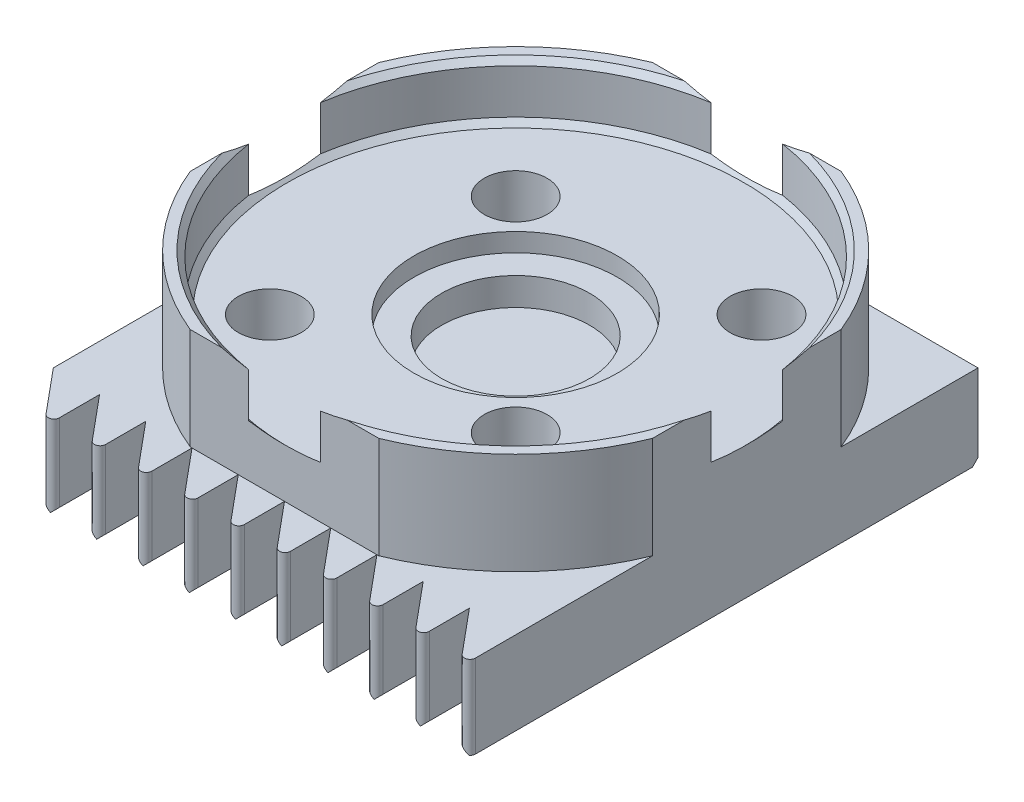
SolidWorks part; units mm, degrees
ref_plane "Front Plane" through (0, 0, 0) normal (0, 0, 1) x (1, 0, 0)
ref_plane "Top Plane" through (0, 0, 0) normal (0, 1, 0) x (1, 0, 0)
ref_plane "Right Plane" through (0, 0, 0) normal (1, 0, 0) x (0, 0, -1)
sketch "Sketch1" plane through (0, 0, 0) normal (0, 1, 0) x (1, 0, 0)
  line L0 (-6.6468, -6.6468) -> (6.6468, 6.6468) construction
  line L1 (-5.5331, 5.5331) -> (5.5331, -5.5331) construction
  line L2 (0, 0) -> (0, 3.1277) construction
  circle A0 centre (0, 0) radius 13.5
  circle A1 centre (0, 0) radius 5.5
  circle A2 centre (0, 0) radius 7.825 construction
  circle A3 centre (-5.5331, 5.5331) radius 1.7
  circle A4 centre (5.5331, -5.5331) radius 1.7
  circle A5 centre (0, 0) radius 9.4 construction
  circle A6 centre (-6.6468, -6.6468) radius 1.7
  circle A7 centre (6.6468, 6.6468) radius 1.7
  dimension "D1" = 27
  dimension "D2" = 11
  dimension "D3" = 15.65
  dimension "D4" = 18.8
  dimension "D5" = 3.4
  dimension "D6" = 45
extrude "Boss-Extrude1" add sketch "Sketch1" along normal blind 2.5 contours A0 A7 A6 A4 A3 A1 region at (-13.1182, 0, 0)
sketch "Sketch2" plane through (0, 2.5, 0) normal (0, 1, 0) x (1, 0, 0)
  circle A0 centre (0, 0) radius 12.65
  circle M6 centre (0, 0) radius 13.5
extrude "Boss-Extrude2" add sketch "Sketch2" along normal blind 3 contours A0 M6 region at (-13.1182, 2.5, 0)
sketch "Sketch3" plane through (0, 0, 0) normal (0, -1, 0) x (1, 0, 0)
  line L1 (12.5, -12.5) -> (-12.5, -12.5)
  line L2 (12.5, -12.5) -> (12.5, 12.5)
  line L3 (12.5, 12.5) -> (-12.5, 12.5)
  line L4 (-12.5, -12.5) -> (-12.5, 12.5)
  line L5 (12.5, -12.5) -> (-12.5, 12.5) construction
  line L6 (12.5, 12.5) -> (-12.5, -12.5) construction
  circle A0 centre (-5.5331, -5.5331) radius 1.7 construction
  circle A1 centre (6.6468, -6.6468) radius 1.7 construction
  circle A2 centre (5.5331, 5.5331) radius 1.7 construction
  circle A3 centre (-6.6468, 6.6468) radius 1.7 construction
  circle A4 centre (-5.5331, -5.5331) radius 1.7 construction
  circle A5 centre (6.6468, -6.6468) radius 1.7 construction
  circle A6 centre (5.5331, 5.5331) radius 1.7 construction
  circle A7 centre (-6.6468, 6.6468) radius 1.7 construction
  circle A8 centre (-6.6468, 6.6468) radius 3
  circle A9 centre (5.5331, 5.5331) radius 3
  circle A10 centre (6.6468, -6.6468) radius 3
  circle A11 centre (-5.5331, -5.5331) radius 3
  point P0 (0, 0)
  circle M5 centre (0, 0) radius 5.5
  circle M6 centre (0, 0) radius 13.5
  dimension "D1" = 6
  dimension "D2" = 25
extrude "Boss-Extrude3" add sketch "Sketch3" along normal blind 4.5 contours L4 L1 L2 L3 A11 A9 A10 A8 M6 M5 | L4 L3 M6 | L4 L1 M6 | L1 L2 M6 | L2 L3 M6 | A11 A9 M5 region at (10.3804, 0, -10.3804) region at (0, 0, -12.1464) region at (-10.3804, 0, -10.3804) region at (10.3804, 0, 10.3804) region at (-10.3804, 0, 10.3804) region at (0, 0, 0)
chamfer "Chamfer2" distance 0.3 angle 45 1 edges at (0, 2.5, 12.65)
sketch "Sketch4" plane through (0, 0, 0) normal (0, 1, 0) x (1, 0, 0)
  circle A0 centre (0, 0) radius 5.5 construction
  circle A1 centre (0, 0) radius 5.5
  circle A2 centre (0, 0) radius 4
  arc M1 (2.6146, -4.8388) -> (4.8388, -2.6146) centre (5.5331, -5.5331) cw
  arc M2 (4.8388, -2.6146) -> (-2.6146, 4.8388) centre (0, 0) ccw
  arc M3 (-2.6146, 4.8388) -> (-4.8388, 2.6146) centre (-5.5331, 5.5331) cw
  arc M4 (-4.8388, 2.6146) -> (2.6146, -4.8388) centre (0, 0) ccw
  dimension "D1" = 8
extrude "Boss-Extrude4" add sketch "Sketch4" along normal blind 1.5 contours A2 M4 M1 M2 M3 | A1 M3 | A1 M1 region at (5.1813, 0, 1.3103) region at (-3.6647, 0, -3.6647) region at (3.6647, 0, 3.6647)
sketch "Sketch6" plane through (0, 0, 0) normal (0, -1, 0) x (1, 0, 0)
  line L0 (5.099, -12.5) -> (-5.099, -12.5) construction
  line L1 (12.5, 5.099) -> (12.5, -5.099) construction
  line L2 (-5.099, 12.5) -> (5.099, 12.5) construction
  line L3 (-12.5, -5.099) -> (-12.5, 5.099) construction
  line L4 (5.099, -12.5) -> (-5.099, -12.5)
  line L5 (12.5, 5.099) -> (12.5, -5.099)
  line L6 (-5.099, 12.5) -> (5.099, 12.5)
  line L7 (-12.5, -5.099) -> (-12.5, 5.099)
  arc A0 (-5.099, -12.5) -> (5.099, -12.5) centre (0, 0) ccw construction
  arc A1 (12.5, -5.099) -> (12.5, 5.099) centre (0, 0) ccw construction
  arc A2 (5.099, 12.5) -> (-5.099, 12.5) centre (0, 0) ccw construction
  arc A3 (-12.5, 5.099) -> (-12.5, -5.099) centre (0, 0) ccw construction
  arc A4 (-5.099, -12.5) -> (5.099, -12.5) centre (0, 0) ccw
  arc A5 (12.5, -5.099) -> (12.5, 5.099) centre (0, 0) ccw
  arc A6 (5.099, 12.5) -> (-5.099, 12.5) centre (0, 0) ccw
  arc A7 (-12.5, 5.099) -> (-12.5, -5.099) centre (0, 0) ccw
extrude "Cut-Extrude1" cut sketch "Sketch6" against normal through all
chamfer "Chamfer3" distance 0.3 angle 45 4 edges at (8.9449, 5.5, -8.9449) (-8.9449, 5.5, -8.9449) (-8.9449, 5.5, 8.9449) (8.9449, 5.5, 8.9449)
sketch "Sketch7" plane through (0, -4.5, 0) normal (0, -1, 0) x (1, 0, 0)
  line L0 (12.5, 12.5) -> (-12.5, 12.5) construction
  line L1 (12.5, 12.5) -> (-12.5, 12.5)
  line L2 (-12.5, 12.5) -> (-10, 15.5)
  line L3 (-10, 15.5) -> (-10, 12.5)
  line L4 (-7.5, 15.5) -> (-7.5, 12.5)
  line L5 (-10, 12.5) -> (-7.5, 15.5)
  line L6 (-5, 15.5) -> (-5, 12.5)
  line L7 (-7.5, 12.5) -> (-5, 15.5)
  line L8 (-2.5, 15.5) -> (-2.5, 12.5)
  line L9 (-5, 12.5) -> (-2.5, 15.5)
  line L10 (0, 15.5) -> (0, 12.5)
  line L11 (-2.5, 12.5) -> (0, 15.5)
  line L12 (2.5, 15.5) -> (2.5, 12.5)
  line L13 (0, 12.5) -> (2.5, 15.5)
  line L14 (5, 15.5) -> (5, 12.5)
  line L15 (2.5, 12.5) -> (5, 15.5)
  line L16 (7.5, 15.5) -> (7.5, 12.5)
  line L17 (5, 12.5) -> (7.5, 15.5)
  line L18 (10, 15.5) -> (10, 12.5)
  line L19 (7.5, 12.5) -> (10, 15.5)
  line L20 (12.5, 15.5) -> (12.5, 12.5)
  line L21 (10, 12.5) -> (12.5, 15.5)
  line M9 (12.5, 12.5) -> (-12.5, 12.5)
  dimension "D1" = 3
  dimension "D2" = 2.5
  dimension "D3" = 10
extrude "Boss-Extrude5" add sketch "Sketch7" against normal up to surface (4.5 mm away) contours L3 L2 L1 | L5 L1 L4 | L7 L1 L6 | L9 L1 L8 | L11 L1 L10 | L13 L1 L12 | L15 L1 L14 | L17 L1 L16 | L19 L1 L18 | L21 L20 M9 region at (-10.8333, -4.5, 13.5) region at (-8.3333, -4.5, 13.5) region at (-5.8333, -4.5, 13.5) region at (-3.3333, -4.5, 13.5) region at (-0.8333, -4.5, 13.5) region at (1.6667, -4.5, 13.5) region at (4.1667, -4.5, 13.5) region at (6.6667, -4.5, 13.5) region at (9.1667, -4.5, 13.5) region at (11.6667, -4.5, 13.5)
chamfer "Chamfer4" distance 0.3 angle 45 20 edges at (0, -4.5, -12.5) (11.25, -4.5, 14) (10, -4.5, 14) (8.75, -4.5, 14) (7.5, -4.5, 14) (6.25, -4.5, 14) (5, -4.5, 14) (3.75, -4.5, 14) (2.5, -4.5, 14) (1.25, -4.5, 14) (0, -4.5, 14) (-1.25, -4.5, 14) (-2.5, -4.5, 14) (-3.75, -4.5, 14) (-5, -4.5, 14) (-6.25, -4.5, 14) (-7.5, -4.5, 14) (-8.75, -4.5, 14) (-10, -4.5, 14) (-11.25, -4.5, 14)
fillet "Fillet1" radius 0.3 10 edges at (10, -2.1, 15.5) (7.5, -2.1, 15.5) (5, -2.1, 15.5) (2.5, -2.1, 15.5) (0, -2.1, 15.5) (-2.5, -2.1, 15.5) (-5, -2.1, 15.5) (-7.5, -2.1, 15.5) (-10, -2.1, 15.5) (12.5, -2.1, 15.5)
sketch "Sketch8" plane through (0, -4.5, 0) normal (0, -1, 0) x (1, 0, 0)
  line L0 (0, -6) -> (0, 6) construction
  circle A0 centre (0, 6) radius 1.2
  circle A1 centre (0, -6) radius 1.2
  dimension "D1" = 6
  dimension "D2" = 2.4
extrude "Cut-Extrude2" cut sketch "Sketch8" against normal blind 3
chamfer "Chamfer5" distance 2 angle 45 4 edges at (6.6468, 0, -9.6468) (-5.5331, 0, -8.5331) (5.5331, 0, 2.5331) (-6.6468, 0, 3.6468)
